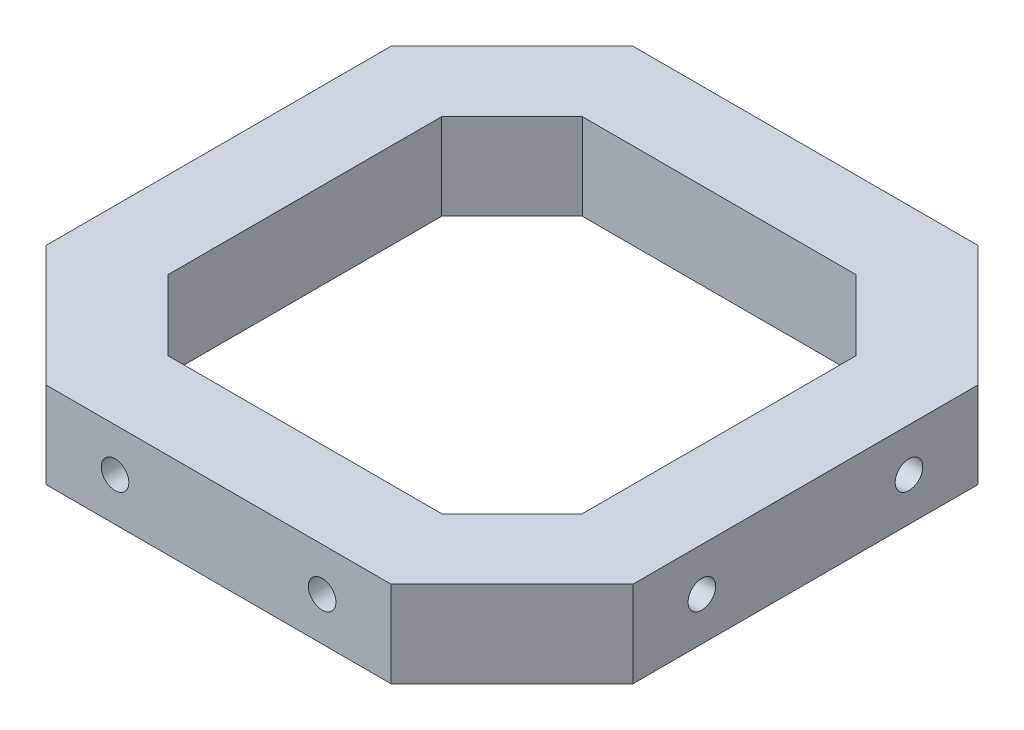
SolidWorks part; units mm, degrees
ref_plane "前视基准面" through (0, 0, 0) normal (0, 0, 1) x (1, 0, 0)
ref_plane "上视基准面" through (0, 0, 0) normal (0, 1, 0) x (1, 0, 0)
ref_plane "右视基准面" through (0, 0, 0) normal (1, 0, 0) x (0, 0, -1)
other "Configuration Table"
sketch "草图1" plane through (0, 0, 0) normal (0, 1, 0) x (1, 0, 0)
  line L0 (-17, 10) -> (-17, -10)
  line L5 (17, 10) -> (10, 17)
  line L6 (10, 17) -> (-10, 17)
  line L7 (-10, 17) -> (-17, 10)
  line L9 (-10, -17) -> (10, -17)
  line L11 (-10, 17) -> (-10, -17) construction
  line L12 (10, 17) -> (10, -17) construction
  line L13 (-17, -10) -> (-10, -17)
  line L14 (17, 10) -> (17, -10)
  line L15 (17, -10) -> (10, -17)
  line L16 (-17, 10) -> (17, 10) construction
  line L17 (-17, -10) -> (17, -10) construction
  line L18 (-7.9289, 12) -> (-12, 7.9289)
  line L19 (-12, 7.9289) -> (-12, -7.9289)
  line L20 (-12, -7.9289) -> (-7.9289, -12)
  line L21 (-7.9289, -12) -> (7.9289, -12)
  line L22 (7.9289, -12) -> (12, -7.9289)
  line L23 (12, -7.9289) -> (12, 7.9289)
  line L24 (12, 7.9289) -> (7.9289, 12)
  line L25 (7.9289, 12) -> (-7.9289, 12)
  point P0 (0, 10)
  point P11 (-17, 0)
  point P25 (13.5, -13.5)
  dimension "D3" = 5
  dimension "D1" = 34
  dimension "D2" = 20
  dimension "D4" = 5
  dimension "D5" = 5
  dimension "D6" = 5
  dimension "D7" = 5
extrude "凸台-拉伸1" add sketch "草图1" along normal blind 5 contours L5 L6 L7 L0 L13 L9 L15 L14 | L21 L22 L23 L24 L25 L18 L19 L20
sketch "草图2" plane through (0, 0, -17) normal (0, 0, -1) x (-1, 0, 0)
  line L0 (10, 5) -> (10, 0) construction
  line L1 (-10, 5) -> (-10, 0) construction
  circle A0 centre (6, 2.5) radius 0.8
  circle A1 centre (-6, 2.5) radius 0.8
  point P6 (10, 2.5)
  dimension "D3" = 1.6
  dimension "D1" = 4
  dimension "D2" = 4
extrude "切除-拉伸1" cut sketch "草图2" against normal blind 3 contours A0 | A1
extrude "切除-拉伸2" cut sketch "草图2<3>" along normal blind 3 from surface starting at face at (0, 2.5, 17)
sketch "草图2<3>" plane through (0, 0, -17) normal (0, 0, -1) x (-1, 0, 0) same geometry as "草图2"
sketch "草图3" plane through (-17, 0, 0) normal (-1, 0, 0) x (0, 0, 1)
  line L0 (-10, 5) -> (-10, 0) construction
  line L1 (10, 5) -> (10, 0) construction
  circle A0 centre (-6, 2.5) radius 0.8
  circle A1 centre (6, 2.5) radius 0.8
  point P7 (-10, 2.5)
  dimension "D3" = 1.6
  dimension "D1" = 4
  dimension "D2" = 4
extrude "切除-拉伸3" cut sketch "草图3" against normal blind 3
extrude "切除-拉伸4" cut sketch "草图3<2>" along normal blind 3 from surface starting at face at (17, 2.5, 0)
sketch "草图3<2>" plane through (-17, 0, 0) normal (-1, 0, 0) x (0, 0, 1) same geometry as "草图3"
